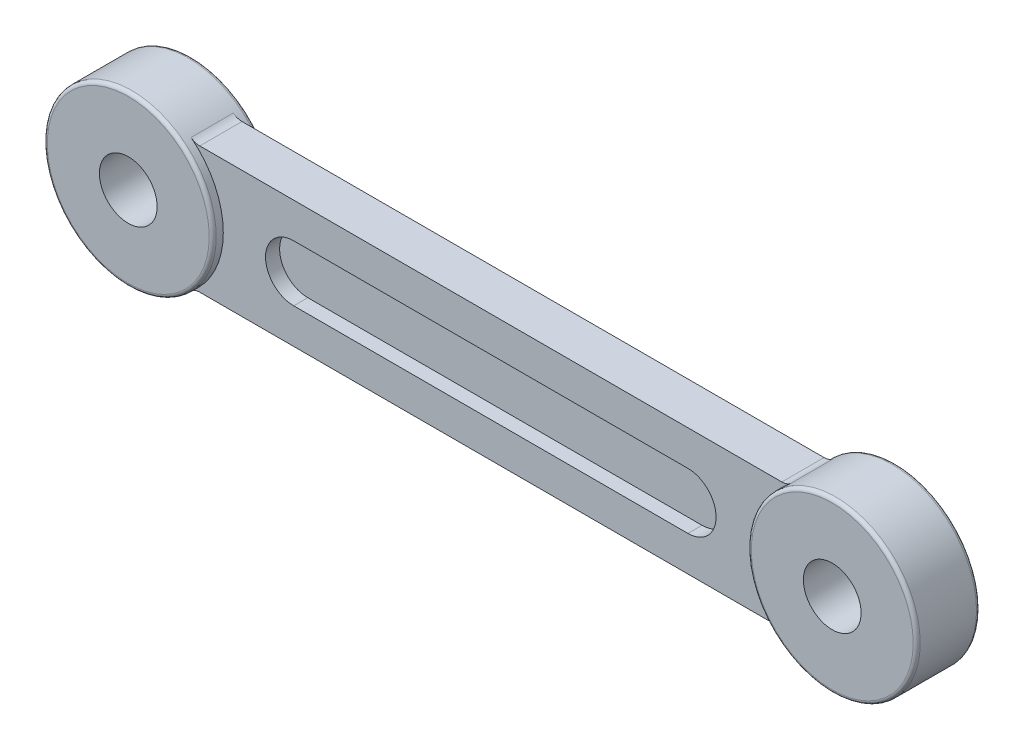
SolidWorks part; units mm, degrees
ref_plane "前视基准面" through (0, 0, 0) normal (0, 0, 1) x (1, 0, 0)
ref_plane "上视基准面" through (0, 0, 0) normal (0, 1, 0) x (1, 0, 0)
ref_plane "右视基准面" through (0, 0, 0) normal (1, 0, 0) x (0, 0, -1)
other "Configuration Table"
sketch "草图1" plane through (0, 0, 0) normal (0, 0, 1) x (1, 0, 0)
  line L0 (-50, 0) -> (50, 0) construction
  line L1 (-42.0627, 9) -> (42.0627, 9)
  line L2 (-50, 9) -> (-50, -9) construction
  line L3 (-42.0627, -9) -> (42.0627, -9)
  line L4 (50, 9) -> (50, -9) construction
  line L5 (-50, 9) -> (50, -9) construction
  line L6 (-50, -9) -> (50, 9) construction
  line L7 (42.0627, 9) -> (50, 9) construction
  line L8 (42.0627, -9) -> (50, -9) construction
  line L9 (-50, -9) -> (-42.0627, -9) construction
  line L10 (-50, 9) -> (-42.0627, 9) construction
  circle A0 centre (-50, 0) radius 12
  circle A1 centre (50, 0) radius 12
  circle A2 centre (-50, 0) radius 4.1
  circle A3 centre (50, 0) radius 4.1
  point P0 (0, 0)
  point P14 (-42.0627, 9)
  point P15 (-42.0627, -9)
  point P16 (42.0627, -9)
  point P17 (42.0627, 9)
  dimension "D3" = 24
  dimension "D4" = 24
  dimension "D5" = 8.2
  dimension "D6" = 8.2
  dimension "D1" = 100
  dimension "D2" = 18
extrude "凸台-拉伸1" add sketch "草图1" along normal blind 3 and the other way blind 3 contours A1 L1 A0 L3 region at (0, 0, 0)
extrude "凸台-拉伸2" add sketch "草图1<3>" along normal blind 4.5 and the other way blind 4.5 contours A0 A2 | A1 A3 region at (-39.3721, 4.7976, 0) region at (54.7976, 10.6279, 0)
sketch "草图1<3>" plane through (0, 0, 0) normal (0, 0, 1) x (1, 0, 0) same geometry as "草图1"
fillet "圆角1" radius 2 4 edges at (42.0627, 9, 0) (-42.0627, 9, 0) (42.0627, -9, 0) (-42.0627, -9, 0)
fillet "圆角2" radius 0.5 4 edges at (62, 0, -4.5) (-38, 0, -4.5) (62, 0, 4.5) (-38, 0, 4.5)
sketch "草图2" plane through (0, 0, 3) normal (0, 0, 1) x (1, 0, 0)
  line L0 (-28, 0) -> (28, 0) construction
  line L1 (-28, 4) -> (28, 4)
  line L2 (-28, -4) -> (28, -4)
  arc A0 (-28, 4) -> (-28, -4) centre (-28, 0) ccw
  arc A1 (28, -4) -> (28, 4) centre (28, 0) ccw
  point P2 (0, 0)
  dimension "D1" = 8
  dimension "D2" = 56
extrude "切除-拉伸1" cut sketch "草图2" against normal blind 2
mirror "镜向1" about plane through (0, 0, 0) normal (0, 0, 1) of "切除-拉伸1"
